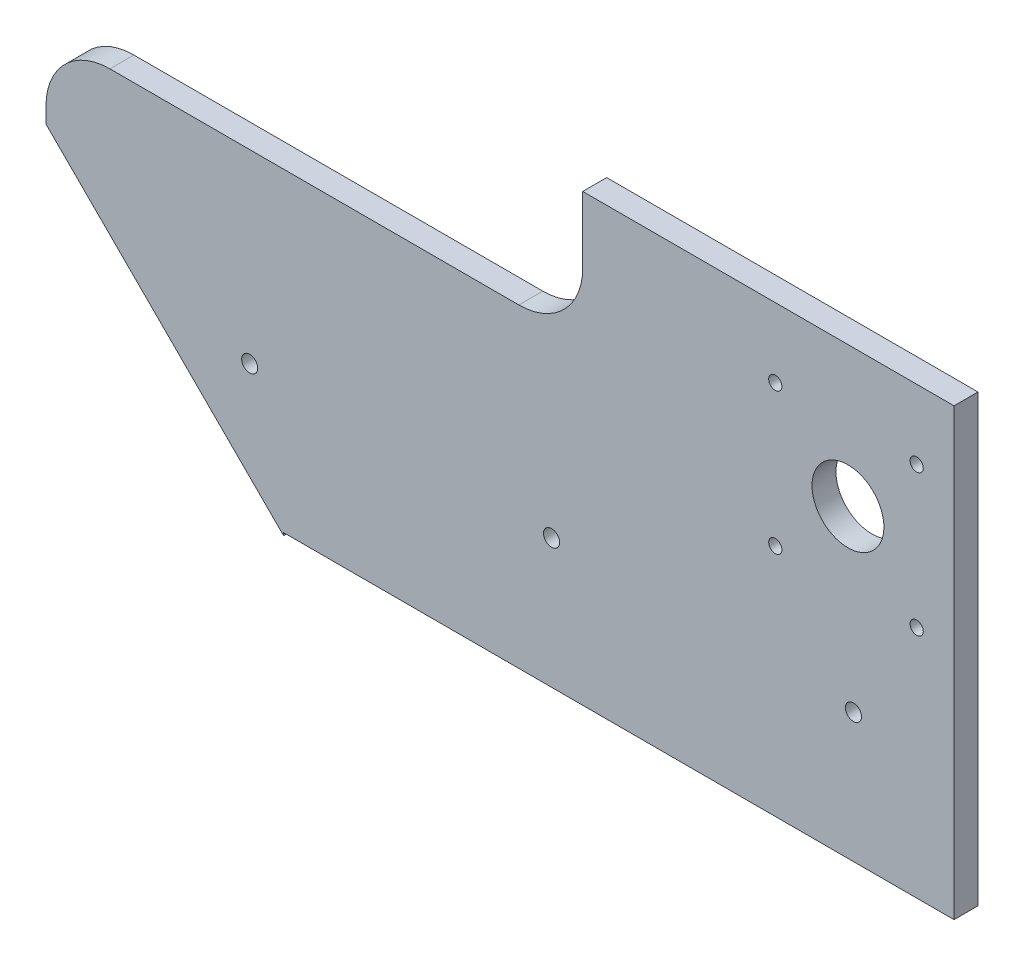
SolidWorks part; units mm, degrees
ref_plane "Front Plane" through (0, 0, 0) normal (0, 0, 1) x (1, 0, 0)
ref_plane "Top Plane" through (0, 0, 0) normal (0, 1, 0) x (1, 0, 0)
ref_plane "Right Plane" through (0, 0, 0) normal (1, 0, 0) x (0, 0, -1)
sketch "Sketch1" plane through (0, 0, 0) normal (0, 0, 1) x (1, 0, 0)
  line L0 (-138.2594, 48.9915) -> (32.2106, -121.4785)
  line L1 (32.2106, -121.4785) -> (222.7106, -121.4785)
  line L2 (-138.2594, 146.2068) -> (-138.2594, 48.9915)
  line L3 (-138.2594, 146.2068) -> (222.7106, 146.2068)
  line L4 (222.7106, -121.4785) -> (222.7106, 146.2068)
  circle A0 centre (180.538, 76.832) radius 14.2875
  circle A2 centre (180.538, 76.832) radius 69.85 construction
  circle A3 centre (180.538, 76.832) radius 318.7974 construction
  point P0 (0, 0)
  point P2 (180.538, 76.832)
  dimension "D4" = 198.3105
  dimension "D1" = 45
  dimension "D2" = 267.6854
  dimension "D5" = 245.11
extrude "Boss-Extrude1" add sketch "Sketch1" along normal blind 9.525
sketch "Sketch2" plane through (0, 0, 9.525) normal (0, 0, 1) x (1, 0, 0)
  line L0 (32.2106, -121.4785) -> (222.7106, -121.4785) construction
  line L1 (241.7606, -121.4785) -> (-43.8123, -121.4785)
  line L2 (241.7606, -121.4785) -> (241.7606, -44.3895)
  line L3 (241.7606, -44.3895) -> (-43.8123, -44.3895)
  line L4 (-43.8123, -121.4785) -> (-43.8123, -44.3895)
extrude "Cut-Extrude1" cut sketch "Sketch2" against normal through all contours L3 L4 L1 L2
sketch "Sketch4" plane through (0, 0, 9.525) normal (0, 0, 1) x (1, 0, 0)
  line L1 (-138.2594, 146.2068) -> (-138.2594, 48.9915) construction
  line L3 (-138.2594, 146.2068) -> (75.1006, 146.2068)
  line L4 (-138.2594, 146.2068) -> (-138.2594, 80.7415)
  line L5 (-138.2594, 80.7415) -> (75.1006, 80.7415)
  line L6 (75.1006, 146.2068) -> (75.1006, 80.7415)
extrude "Cut-Extrude2" cut sketch "Sketch4" against normal through all contours L5 L6 L3 L4
fillet "Fillet2" radius 25.4 2 edges at (-138.2594, 80.7415, 4.7625) (75.1006, 80.7415, 4.7625)
hole_wizard "Ø6.4 (6.4) Diameter Hole2" positions "Sketch15" profile "Sketch14" hole size "Ø6.4" standard "Lanco STD" end condition through all
sketch "Sketch15" plane through (0, 0, 0) normal (0, 0, -1) x (-1, 0, 0)
  line L2 (-222.7106, -44.3895) -> (-222.7106, 146.2068) construction
  point P3 (-182.7106, 7.0429)
  point P6 (-62.7106, 7.0429)
  point P9 (57.2894, 7.0429)
  dimension "D1" = 40
  dimension "D2" = 120
  dimension "D3" = 120
sketch "Sketch14" plane through (182.7106, 7.0429, 0) normal (1, 0, 0) x (0, 1, 0)
  line L0 (0, 0) -> (0, 9.525)
  line L1 (0, 9.525) -> (3.2, 9.525)
  line L2 (3.2, 9.525) -> (3.2, 0)
  line L5 (3.2, 0) -> (0, 0)
  line L11 (0, -6.35) -> (0, 107.95) construction
  dimension "Thru Hole Dia." = 6.4
  dimension "Thru Hole Depth" = 9.525
sketch "Sketch16" plane through (222.7106, 0, 0) normal (1, 0, 0) x (0, 0, -1)
  line L0 (0, -44.3895) -> (0, 146.2068) construction
  line L1 (-9.525, 146.2068) -> (0, 146.2068)
  line L2 (-9.525, 146.2068) -> (-9.525, 145.2215)
  line L3 (-9.525, 145.2215) -> (0, 145.2215)
  line L4 (0, 146.2068) -> (0, 145.2215)
extrude "Cut-Extrude3" cut sketch "Sketch16" against normal through all
sketch "Sketch17" plane through (0, 0, 0) normal (0, 0, -1) x (-1, 0, 0)
  line L0 (-222.7106, -44.3895) -> (-222.7106, 145.2215) construction
  line L1 (-75.1006, 145.2215) -> (-222.7106, 145.2215)
  line L2 (-75.1006, 145.2215) -> (-75.1006, 132.5215)
  line L3 (-75.1006, 132.5215) -> (-222.7106, 132.5215)
  line L4 (-222.7106, 145.2215) -> (-222.7106, 132.5215)
  dimension "D1" = 12.7
extrude "Cut-Extrude4" cut sketch "Sketch17" against normal through all
hole_wizard "Tap Drill for M6x0.75 Tap1" positions "Sketch19" profile "Sketch18" hole size "M6x0.75" standard "Lanco STD" end condition through all
sketch "Sketch19" plane through (0, 0, 9.525) normal (0, 0, 1) x (1, 0, 0)
  point P0 (207.8541, 104.9236)
  point P3 (151.6541, 104.9236)
  point P6 (151.6541, 48.7236)
  point P9 (207.8541, 48.7236)
sketch "Sketch18" plane through (207.8541, 104.9236, 9.525) normal (1, 0, 0) x (0, -1, 0)
  line L0 (0, 0) -> (0, 9.525)
  line L1 (0, 9.525) -> (2.625, 9.525)
  line L2 (2.625, 9.525) -> (2.625, 0)
  line L5 (2.625, 0) -> (0, 0)
  line L11 (0, -6.35) -> (0, 107.95) construction
  dimension "Thru Hole Dia." = 5.25
  dimension "Thru Hole Depth" = 9.525
